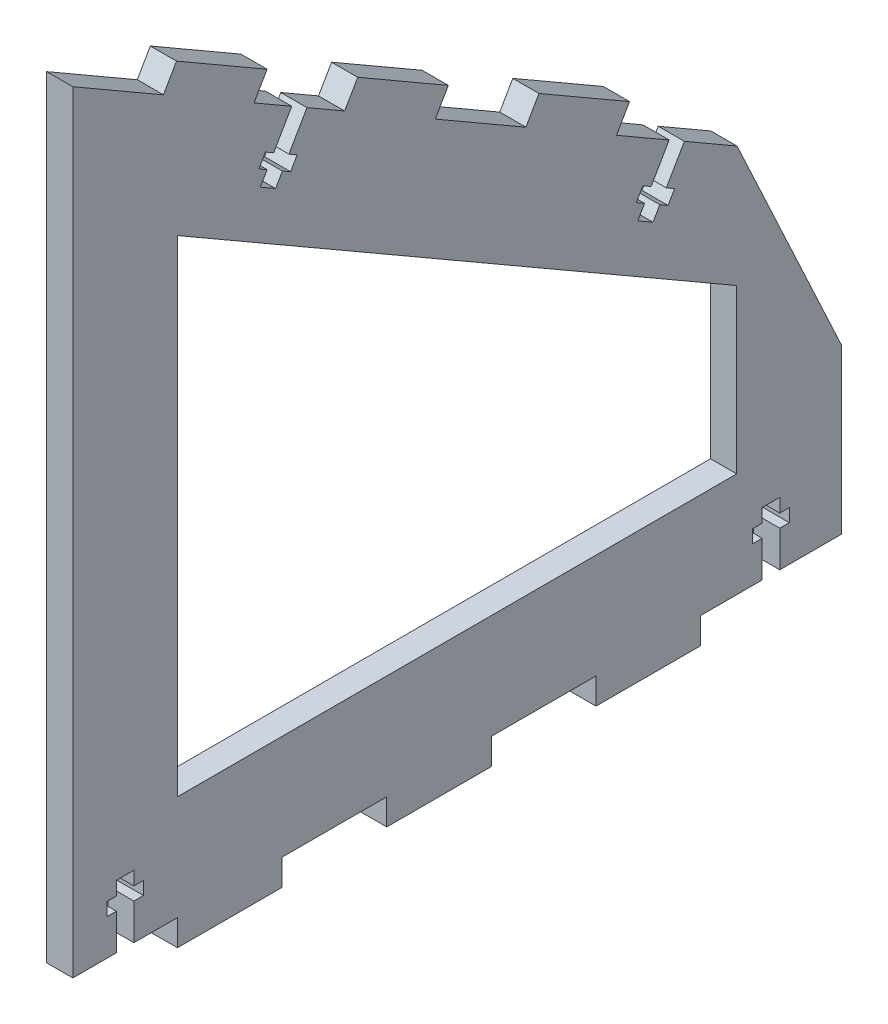
SolidWorks part; units mm, degrees
ref_plane "Front Plane" through (0, 0, 0) normal (0, 0, 1) x (1, 0, 0)
ref_plane "Top Plane" through (0, 0, 0) normal (0, 1, 0) x (1, 0, 0)
ref_plane "Right Plane" through (0, 0, 0) normal (1, 0, 0) x (0, 0, -1)
sketch "Sketch1" plane through (-32.0384, 0, 0) normal (-1, 0, 0) x (0, 0, 1)
  line L0 (-215.9, 95.25) -> (-215.9, 174.9125)
  line L1 (165.3114, 95.25) -> (-83.5343, 95.25) construction
  line L2 (-215.9, 174.9125) -> (-29.3333, 282.6268)
  line L3 (-29.3333, 282.6268) -> (-29.3333, 95.25)
  line L4 (-29.3333, 95.25) -> (-215.9, 95.25)
  line L5 (-29.3333, 282.6268) -> (-40.1822, 276.3632) construction
  line L6 (-29.3333, 95.25) -> (-29.3333, 282.6268) construction
extrude "Boss-Extrude1" add sketch "Sketch1" along normal mid plane 6.35
sketch "Sketch2" plane through (-35.2134, 0, 0) normal (-1, 0, 0) x (0, 0, 1)
  line L4 (-190.5, 160.2478) -> (-190.5, 120.65)
  line L5 (-190.5, 160.2478) -> (-190.5, 120.65)
  line L14 (-54.7333, 120.65) -> (-54.7333, 238.6327)
  line L15 (-190.5, 120.65) -> (-54.7333, 120.65)
  line L16 (-54.7333, 238.6327) -> (-190.5, 160.2478)
  line L17 (-54.7333, 120.65) -> (-54.7333, 238.6327)
  line L18 (-190.5, 120.65) -> (-54.7333, 120.65)
  line L19 (-54.7333, 238.6327) -> (-190.5, 160.2478)
  dimension "D1" = 25.4
extrude "Cut-Extrude1" cut sketch "Sketch2" against normal blind 6.35
sketch "Sketch4" plane through (0, 95.25, 0) normal (0, -1, 0) x (1, 0, 0)
  line L0 (-35.2134, -215.9) -> (-35.2134, -29.3333) construction
  line L1 (-35.2134, -54.7333) -> (-28.8634, -54.7333)
  line L2 (-35.2134, -54.7333) -> (-35.2134, -80.1333)
  line L3 (-35.2134, -80.1333) -> (-28.8634, -80.1333)
  line L4 (-28.8634, -54.7333) -> (-28.8634, -80.1333)
  line L5 (-28.8634, -215.9) -> (-28.8634, -29.3333) construction
  dimension "D1" = 25.4
  dimension "D2" = 25.4
extrude "Boss-Extrude3" add sketch "Sketch4" along normal blind 6.35
pattern_linear "LPattern2" count 3 spacing 50.8 along (0, 0, -1) of "Boss-Extrude3"
sketch "Sketch5" plane through (-28.8634, 0, 0) normal (1, 0, 0) x (0, 0, -1)
  line L0 (215.9, 95.25) -> (-165.3114, 95.25) construction
  line L1 (198.8167, 95.25) -> (198.8167, 119.6237) construction
  line L2 (215.9, 95.25) -> (181.7333, 95.25) construction
  line L3 (42.0333, 95.25) -> (42.0333, 127.2639) construction
  line L4 (54.7333, 95.25) -> (29.3333, 95.25) construction
  line L5 (83.5343, 95.25) -> (-165.3114, 95.25) construction
  line B0 (196.6831, 95.25) -> (200.9503, 95.25)
  line B1 (200.9503, 107.188) -> (203.2617, 107.188)
  line B2 (203.2617, 107.188) -> (203.2617, 104.013)
  line B3 (203.2617, 104.013) -> (200.9503, 104.013)
  line B4 (200.9503, 104.013) -> (200.9503, 95.25)
  line B5 (200.9503, 107.188) -> (200.9503, 110.49)
  line B6 (200.9503, 110.49) -> (196.6831, 110.49)
  line B7 (196.6831, 107.188) -> (196.6831, 110.49)
  line B8 (196.6831, 104.013) -> (196.6831, 95.25)
  line B9 (194.3717, 104.013) -> (196.6831, 104.013)
  line B10 (194.3717, 107.188) -> (194.3717, 104.013)
  line B11 (196.6831, 107.188) -> (194.3717, 107.188)
  line B12 (39.8997, 95.25) -> (44.1669, 95.25)
  line B13 (44.1669, 107.188) -> (46.4783, 107.188)
  line B14 (46.4783, 107.188) -> (46.4783, 104.013)
  line B15 (46.4783, 104.013) -> (44.1669, 104.013)
  line B16 (44.1669, 104.013) -> (44.1669, 95.25)
  line B17 (44.1669, 107.188) -> (44.1669, 110.49)
  line B18 (44.1669, 110.49) -> (39.8997, 110.49)
  line B19 (39.8997, 107.188) -> (39.8997, 110.49)
  line B20 (39.8997, 104.013) -> (39.8997, 95.25)
  line B21 (37.5883, 104.013) -> (39.8997, 104.013)
  line B22 (37.5883, 107.188) -> (37.5883, 104.013)
  line B23 (39.8997, 107.188) -> (37.5883, 107.188)
sketch_block_instance "TSlot-1"
sketch_block "TSlot" parameters "D1"=3.302, "D2"=3.175
sketch_block_instance "TSlot-3"
extrude "Cut-Extrude2" cut sketch "Sketch5" against normal blind 6.35
ref_plane "Plane1" through (60.9209, 282.9648, -3.0489) normal (-0.1825, -0.9661, 0.1825) x (-0.9832, 0.1793, -0.0339)
sketch "Sketch7" plane through (0, 224.6718, -129.7143) normal (0, 0.866, -0.5) x (1, 0, 0)
  line L0 (-28.8634, -115.91) -> (-28.8634, 99.5186) construction
  line L1 (-28.8634, -90.51) -> (-35.2134, -90.51)
  line L2 (-28.8634, -90.51) -> (-28.8634, -65.11)
  line L3 (-28.8634, -65.11) -> (-35.2134, -65.11)
  line L4 (-35.2134, -90.51) -> (-35.2134, -65.11)
  line L5 (-35.2134, -115.91) -> (-35.2134, 99.5186) construction
  line L6 (-35.2134, -115.91) -> (-28.8634, -115.91) construction
  point P8 (-32.0384, -115.91)
  dimension "D1" = 25.4
  dimension "D2" = 25.4
extrude "Boss-Extrude4" add sketch "Sketch7" along normal blind 6.35
pattern_linear "LPattern3" count 3 spacing 50.8 along (0, -0.5, -0.866) of "Boss-Extrude4"
sketch "Sketch8" plane through (-35.2134, 0, 0) normal (-1, 0, 0) x (0, 0, 1)
  line L1 (-73.3274, 257.2268) -> (-95.3245, 244.5268) construction
  line L2 (-84.326, 250.8768) -> (-74.3177, 233.542) construction
  line L3 (-161.3156, 206.4268) -> (-190.5849, 189.5282) construction
  line L4 (-161.3156, 206.4268) -> (-215.9, 174.9125) construction
  line L5 (-215.9, 135.0812) -> (-190.5849, 189.5282)
  line L6 (-215.9, 174.9125) -> (-215.9, 95.25) construction
  line L7 (-215.9, 135.0812) -> (-215.9, 174.9125)
  line L8 (-215.9, 174.9125) -> (-190.5849, 189.5282)
  line L9 (-175.9503, 197.9775) -> (-169.2761, 186.4175) construction
  line B0 (-82.4782, 251.9436) -> (-86.1737, 249.81)
  line B1 (-80.2047, 239.4714) -> (-82.2064, 238.3157)
  line B2 (-82.2064, 238.3157) -> (-83.7939, 241.0653)
  line B3 (-83.7939, 241.0653) -> (-81.7922, 242.221)
  line B4 (-81.7922, 242.221) -> (-86.1737, 249.81)
  line B5 (-80.2047, 239.4714) -> (-78.5537, 236.6118)
  line B6 (-78.5537, 236.6118) -> (-74.8582, 238.7454)
  line B7 (-76.5092, 241.605) -> (-74.8582, 238.7454)
  line B8 (-78.0967, 244.3546) -> (-82.4782, 251.9436)
  line B9 (-76.095, 245.5103) -> (-78.0967, 244.3546)
  line B10 (-74.5075, 242.7607) -> (-76.095, 245.5103)
  line B11 (-76.5092, 241.605) -> (-74.5075, 242.7607)
  line B12 (-174.1025, 199.0443) -> (-177.798, 196.9107)
  line B13 (-171.829, 186.5721) -> (-173.8308, 185.4164)
  line B14 (-173.8308, 185.4164) -> (-175.4183, 188.166)
  line B15 (-175.4183, 188.166) -> (-173.4165, 189.3217)
  line B16 (-173.4165, 189.3217) -> (-177.798, 196.9107)
  line B17 (-171.829, 186.5721) -> (-170.178, 183.7125)
  line B18 (-170.178, 183.7125) -> (-166.4825, 185.8461)
  line B19 (-168.1335, 188.7057) -> (-166.4825, 185.8461)
  line B20 (-169.721, 191.4553) -> (-174.1025, 199.0443)
  line B21 (-167.7193, 192.611) -> (-169.721, 191.4553)
  line B22 (-166.1318, 189.8614) -> (-167.7193, 192.611)
  line B23 (-168.1335, 188.7057) -> (-166.1318, 189.8614)
sketch_block_instance "TSlot-6"
sketch_block_instance "TSlot-8"
extrude "Cut-Extrude3" cut sketch "Sketch8" against normal through all both and the other way through all
